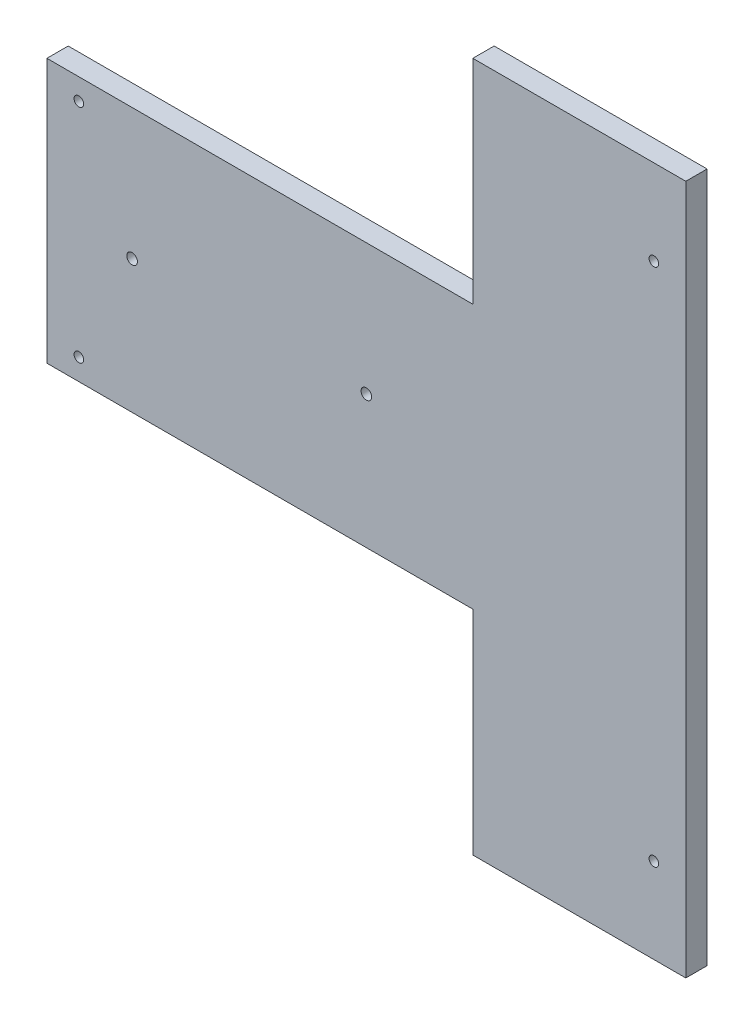
SolidWorks part; units mm, degrees
ref_plane "Plan de face" through (0, 0, 0) normal (0, 0, 1) x (1, 0, 0)
ref_plane "Plan de dessus" through (0, 0, 0) normal (0, 1, 0) x (1, 0, 0)
ref_plane "Plan de droite" through (0, 0, 0) normal (1, 0, 0) x (0, 0, -1)
sketch "Esquisse1" plane through (0, 0, 0) normal (0, 0, 1) x (1, 0, 0)
  line L1 (-122.4446, 41.9355) -> (177.5554, 41.9355)
  line L2 (-122.4446, 41.9355) -> (-122.4446, -82.0645)
  line L3 (-122.4446, -82.0645) -> (177.5554, -82.0645)
  line L4 (177.5554, 41.9355) -> (177.5554, -82.0645)
  line L5 (177.5554, -82.0645) -> (77.5554, -82.0645)
  line L6 (177.5554, -82.0645) -> (177.5554, -182.0645)
  line L7 (177.5554, -182.0645) -> (77.5554, -182.0645)
  line L8 (77.5554, -82.0645) -> (77.5554, -182.0645)
  line L9 (177.5554, 41.9355) -> (77.5554, 41.9355)
  line L10 (177.5554, 41.9355) -> (177.5554, 141.9355)
  line L11 (177.5554, 141.9355) -> (77.5554, 141.9355)
  line L12 (77.5554, 41.9355) -> (77.5554, 141.9355)
  dimension "D1" = 300
  dimension "D2" = 124
  dimension "D3" = 100
  dimension "D4" = 100
  dimension "D5" = 100
  dimension "D6" = 100
extrude "Boss.-Extru.1" add sketch "Esquisse1" along normal blind 10 contours L10 L1 L5 L7 | L4 L1 L2 L3 | L3 L12 L8 L6 region at (27.5554, -20.0645, 0) region at (127.5554, 91.9355, 0) region at (127.5554, -132.0645, 0)
sketch "Esquisse2" plane through (0, 0, 0) normal (0, 0, -1) x (-1, 0, 0)
  line L0 (-177.5554, -182.0645) -> (-177.5554, 141.9355) construction
  line L1 (-177.5554, -182.0645) -> (-77.5554, -182.0645) construction
  line L2 (-177.5554, 141.9355) -> (-77.5554, 141.9355) construction
  line L3 (122.4446, 41.9355) -> (122.4446, -82.0645) construction
  line L4 (122.4446, 41.9355) -> (-77.5554, 41.9355) construction
  line L5 (122.4446, -82.0645) -> (-77.5554, -82.0645) construction
  circle A0 centre (-162.5554, -142.0645) radius 2.25
  circle A1 centre (-162.5554, 101.9355) radius 2.25
  circle A2 centre (107.4446, 31.9355) radius 2.25
  circle A3 centre (107.4446, -72.0645) radius 2.25
  dimension "D1" = 4.5
  dimension "D2" = 4.5
  dimension "D3" = 4.5
  dimension "D4" = 4.5
  dimension "D5" = 15
  dimension "D6" = 40
  dimension "D7" = 40
  dimension "D8" = 15
  dimension "D10" = 10
  dimension "D11" = 15
  dimension "D12" = 10
  dimension "D9" = 15
extrude "Enlèv. mat.-Extru.1" cut sketch "Esquisse2" against normal blind 10
sketch "Esquisse3" plane through (0, 0, 0) normal (0, 0, -1) x (-1, 0, 0)
  line L0 (122.4446, -82.0645) -> (-77.5554, -82.0645) construction
  line L1 (122.4446, 41.9355) -> (122.4446, -82.0645) construction
  circle A0 centre (-27.5554, -19.5645) radius 2.5
  circle A1 centre (82.4446, -19.5645) radius 2.5
  dimension "D1" = 5
  dimension "D2" = 5
  dimension "D3" = 62.5
  dimension "D4" = 62.5
  dimension "D5" = 40
  dimension "D6" = 110
extrude "Enlèv. mat.-Extru.2" cut sketch "Esquisse3" against normal blind 10
